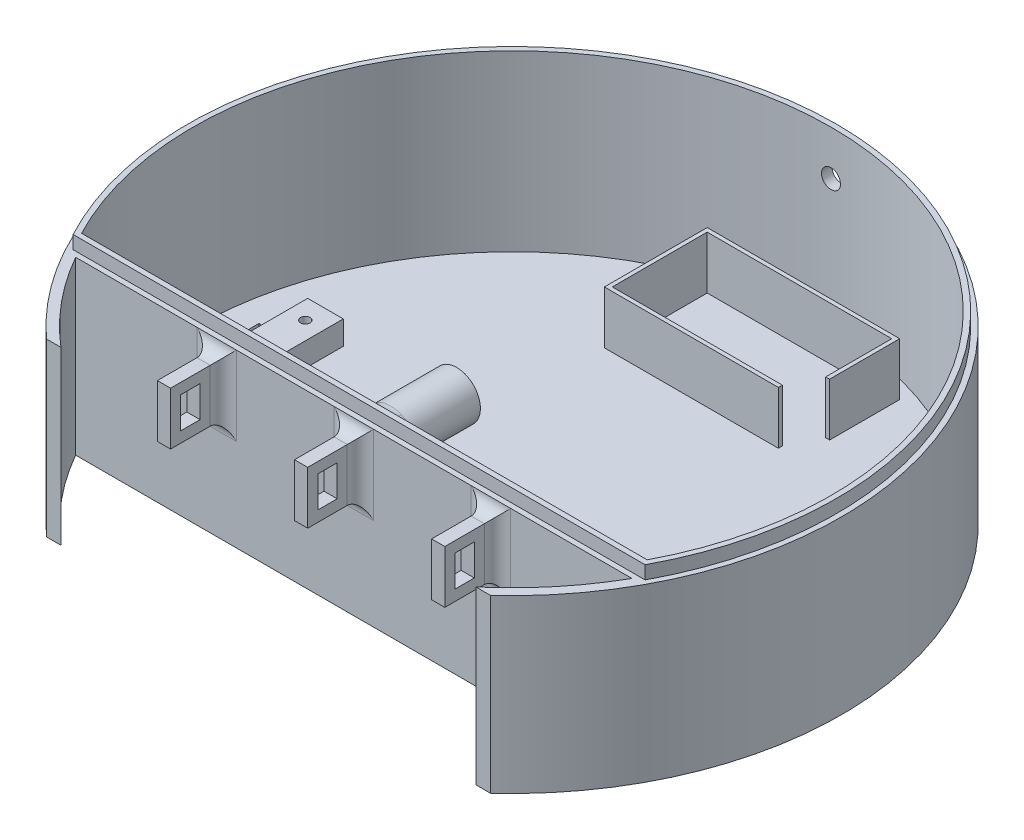
SolidWorks part; units mm, degrees
ref_plane "Plano frontal" through (0, 0, 0) normal (0, 0, 1) x (1, 0, 0)
ref_plane "Plano superior" through (0, 0, 0) normal (0, 1, 0) x (1, 0, 0)
ref_plane "Plano direito" through (0, 0, 0) normal (1, 0, 0) x (0, 0, -1)
sketch "Esboço1" plane through (0, 0, 0) normal (0, 1, 0) x (1, 0, 0)
  line L0 (-109.6586, -60) -> (109.6586, -60)
  circle A0 centre (0, 0) radius 125
  point P5 (0, -125)
  dimension "D1" = 250
  dimension "D2" = 65
extrude "Ressalto-extrusão1" add sketch "Esboço1" along normal blind 70 contours L0 A0 region at (0, 0, -22.5722)
sketch "Esboço5" plane through (0, 70, 0) normal (0, 1, 0) x (1, 0, 0)
  line L1 (-84.2002, -92.3868) -> (-78.7002, -92.3868)
  line L2 (-109.6586, -60) -> (109.6586, -60) construction
  line L3 (78.7002, -92.3868) -> (84.2002, -92.3868)
  line L4 (105.4943, -60) -> (109.6586, -60)
  line L5 (-109.6586, -60) -> (-105.4943, -60)
  arc A0 (-109.6586, -60) -> (-84.2002, -92.3868) centre (0, 0) ccw
  arc A1 (109.6586, -60) -> (84.2002, -92.3868) centre (0, 0) cw
  arc A2 (-105.4943, -60) -> (-78.7002, -92.3868) centre (0, 0) ccw
  arc A3 (78.7002, -92.3868) -> (105.4943, -60) centre (0, 0) ccw
  dimension "D1" = 5.5
  dimension "D2" = 5.5
extrude "Ressalto-extrusão4" add sketch "Esboço5" against normal up to surface (70 mm away) contours A2 L1 A0 L5 | A1 L3 A3 L4 up to face at (0, 0, -32.5)
shell "Casca1" thickness 4 removed face at (0, 70, 45.7497)
sketch "Esboço17" plane through (0, 4, 0) normal (0, 1, 0) x (1, 0, 0)
  line L0 (0, 0) -> (-50000, 0) construction
  line L1 (0, 0) -> (0, 50000) construction
  line L2 (-110, -14) -> (-100, -14)
  line L3 (-110, -14) -> (-110, 14)
  line L4 (-110, 14) -> (-100, 14)
  line L5 (-100, -14) -> (-100, 14)
  line L6 (-110, -14) -> (-100, 14) construction
  line L7 (-110, 14) -> (-100, -14) construction
  line L8 (110, 14) -> (100, -14) construction
  line L9 (110, -14) -> (100, 14) construction
  line L10 (100, -14) -> (100, 14)
  line L11 (110, 14) -> (100, 14)
  line L12 (110, -14) -> (110, 14)
  line L13 (110, -14) -> (100, -14)
  point P3 (-105, 0)
  point P15 (105, 0)
  dimension "D3" = 100
  dimension "D1" = 10
  dimension "D2" = 28
extrude "Corte-extrusão2" cut sketch "Esboço17" against normal blind 10
sketch "Esboço23" plane through (0, 70, 0) normal (0, 1, 0) x (1, 0, 0)
  line L7 (-108.4666, -58) -> (108.4666, -58)
  line L8 (-108.4666, -58) -> (108.4666, -58)
  arc A7 (108.4666, -58) -> (-108.4666, -58) centre (0, 0) ccw
  arc A8 (108.4666, -58) -> (-108.4666, -58) centre (0, 0) ccw
  dimension "D1" = 2
extrude "Corte-extrusão6" cut sketch "Esboço23" along normal blind 4 and the other way blind 5 flip side to cut
sketch "Esboço24" plane through (0, 4, 0) normal (0, 1, 0) x (1, 0, 0)
  line L0 (0, 0) -> (0, 50000) construction
  line L1 (-36.5, 91.0087) -> (49963.5, 91.0087) construction
  line L2 (-36.5, 110.5087) -> (36.5, 110.5087)
  line L3 (-36.5, 110.5087) -> (-36.5, 71.5087)
  line L4 (-36.5, 71.5087) -> (36.5, 71.5087)
  line L5 (36.5, 110.5087) -> (36.5, 71.5087)
  line L7 (35, 109.0087) -> (-35, 109.0087)
  line L8 (35, 109.0087) -> (35, 73.0087)
  line L9 (35, 73.0087) -> (-35, 73.0087)
  line L10 (-35, 109.0087) -> (-35, 73.0087)
  line L11 (35, 109.0087) -> (-35, 73.0087) construction
  line L12 (35, 73.0087) -> (-35, 109.0087) construction
  point P4 (-36.5, 91.0087)
  point P9 (0, 91.0087)
  dimension "D1" = 73
  dimension "D2" = 39
  dimension "D3" = 36.5
  dimension "D4" = 36.5
  dimension "D5" = 70
  dimension "D6" = 36
sketch "Esboço27" plane through (0, 0, 60) normal (0, 0, 1) x (1, 0, 0)
  line L0 (0, 49935) -> (0, -49935) construction
  line L1 (-105.4943, 65) -> (105.4943, 65) construction
  line L2 (104.9883, 32.5) -> (-49895.0117, 32.5) construction
  line L3 (105.4943, 0) -> (105.4943, 65) construction
  line L4 (-26, 82.5) -> (-26, -49917.5) construction
  line L5 (-49.5, 40) -> (-54.5, 40)
  line L6 (-49.5, 40) -> (-49.5, 60)
  line L7 (-49.5, 60) -> (-54.5, 60)
  line L8 (-54.5, 40) -> (-54.5, 60)
  line L9 (-49.5, 40) -> (-54.5, 60) construction
  line L10 (-49.5, 60) -> (-54.5, 40) construction
  line L11 (26, 65) -> (26, -49935) construction
  line L12 (49.5, 60) -> (54.5, 40) construction
  line L13 (49.5, 40) -> (54.5, 60) construction
  line L14 (54.5, 40) -> (54.5, 60)
  line L15 (49.5, 60) -> (54.5, 60)
  line L16 (49.5, 40) -> (49.5, 60)
  line L17 (49.5, 40) -> (54.5, 40)
  line L18 (-2.5, 60) -> (2.5, 40) construction
  line L19 (-2.5, 40) -> (2.5, 60) construction
  line L20 (2.5, 40) -> (2.5, 60)
  line L21 (-2.5, 60) -> (2.5, 60)
  line L22 (-2.5, 40) -> (-2.5, 60)
  line L23 (-2.5, 40) -> (2.5, 40)
  line L24 (-105.4943, 0) -> (105.4943, 0) construction
  point P4 (0, 65)
  point P9 (105.4943, 32.5)
  point P10 (-52, 50)
  point P23 (52, 50)
  point P28 (0, 50)
  point P29 (0, 0)
  point P30 (0, 0)
  dimension "D1" = 5
  dimension "D2" = 20
  dimension "D3" = 26
  dimension "D4" = 26
  dimension "D5" = 52
  dimension "D6" = 40
extrude "Ressalto-extrusão5" add sketch "Esboço27" along normal blind 20
fillet "Filete2" radius 5 12 edges at (52, 60, 60) (49.5, 50, 60) (52, 40, 60) (-52, 60, 60) (-54.5, 50, 60) (-52, 40, 60) (0, 40, 60) (-2.5, 50, 60) (0, 60, 60) (54.5, 50, 60) (2.5, 50, 60) (-49.5, 50, 60)
sketch "Esboço28" plane through (-49.5, 0, 0) normal (1, 0, 0) x (0, 0, -1)
  line L0 (-80, 40) -> (-65, 40) construction
  line L1 (-65, 40) -> (-65, 60) construction
  line L2 (-65, 60) -> (-80, 60) construction
  line L3 (-80, 60) -> (-80, 40) construction
  line L4 (-80, 40) -> (-65, 40) construction
  line L5 (-65, 40) -> (-65, 60) construction
  line L6 (-65, 60) -> (-80, 60) construction
  line L7 (-80, 60) -> (-80, 40) construction
  line L8 (-80, 40) -> (-65, 40)
  line L9 (-65, 40) -> (-65, 60)
  line L10 (-65, 60) -> (-80, 60)
  line L11 (-80, 60) -> (-80, 40)
  line L12 (-80, 40) -> (-65, 40)
  line L13 (-65, 40) -> (-65, 60)
  line L14 (-65, 60) -> (-80, 60)
  line L15 (-80, 60) -> (-80, 40)
  line L16 (-72.5, 42.5) -> (-72.5, -49957.5) construction
  line L17 (-75, 50) -> (49925, 50) construction
  line L18 (-80, 40) -> (-65, 40)
  line L19 (-68.816, 44.0773) -> (-76.184, 44.0773)
  line L20 (-68.816, 44.0773) -> (-68.816, 55.9227)
  line L21 (-68.816, 55.9227) -> (-76.184, 55.9227)
  line L22 (-76.184, 44.0773) -> (-76.184, 55.9227)
  line L23 (-68.816, 44.0773) -> (-76.184, 55.9227) construction
  line L24 (-68.816, 55.9227) -> (-76.184, 44.0773) construction
  line L25 (-65, 40) -> (-65, 60)
  line L26 (-65, 60) -> (-80, 60)
  line L27 (-80, 60) -> (-80, 40)
  line L28 (-80, 40) -> (-65, 40)
  line L29 (-65, 40) -> (-65, 60)
  line L30 (-65, 60) -> (-80, 60)
  line L31 (-80, 60) -> (-80, 40)
  point P6 (-72.5, 60)
  point P9 (-80, 50)
  point P10 (-72.5, 50)
  point P11 (-72.5, 50)
extrude "Corte-extrusão7" cut sketch "Esboço28" against normal blind 5 and the other way blind 104 contours L22 L19 L20 L21 region at (-49.5, 50, 72.5)
sketch "Esboço32" plane through (0, 0, 56) normal (0, 0, -1) x (-1, 0, 0)
  line L0 (0, 0) -> (0, 50000) construction
  line L2 (-105.0373, 53.0583) -> (49894.9627, 53.0583) construction
  circle A0 centre (0, 53.0583) radius 3.6
  circle A1 centre (0, 53.0583) radius 9
extrude "Corte-extrusão8" cut sketch "Esboço32" along normal blind 187 contours A0
extrude "Ressalto-extrusão6" add sketch "Esboço32<3>" along normal blind 35
sketch "Esboço32<3>" plane through (0, 0, 56) normal (0, 0, -1) x (-1, 0, 0) same geometry as "Esboço32"
extrude "Ressalto-extrusão7" add sketch "Esboço32<4>" along normal blind 6 contours A0
sketch "Esboço32<4>" plane through (0, 0, 56) normal (0, 0, -1) x (-1, 0, 0) same geometry as "Esboço32"
fillet "Filete3" radius 10 1 edges at (-9, 53.0583, 56)
extrude "Ressalto-extrusão8" add sketch "Esboço24" along normal blind 20
sketch "Esboço33" plane through (0, 4, 0) normal (0, 1, 0) x (1, 0, 0)
  line L0 (-100, -14) -> (-100, 14) construction
  line L2 (64, -48) -> (4, -48)
  line L3 (64, -48) -> (64, 32)
  line L4 (64, 32) -> (4, 32)
  line L5 (4, -48) -> (4, 32)
  line L8 (-4, -48) -> (-64, -48)
  line L9 (-4, -48) -> (-4, 42)
  line L10 (-4, 42) -> (-64, 42)
  line L11 (-64, -48) -> (-64, 42)
  line L14 (-107.2614, -56) -> (107.2614, -56) construction
  line L15 (100, 14) -> (100, -14) construction
  line L20 (5, 35.3125) -> (65, -45.3125) construction
  line L21 (5, -45.3125) -> (65, 35.3125) construction
  line L26 (-4, 45) -> (-64, -45) construction
  line L27 (-4, -45) -> (-64, 45) construction
  point P0 (35, -5)
  point P9 (-34, 0)
  point P14 (100, 0)
  point P15 (35, -5)
  point P22 (-34, 0)
  dimension "D1" = 8
  dimension "D2" = 36
  dimension "D3" = 60
  dimension "D4" = 60
  dimension "D5" = 90
  dimension "D6" = 36
  dimension "D7" = 80
  dimension "D8" = 8
sketch "Esboço34" plane through (0, 4, 0) normal (0, 1, 0) x (1, 0, 0)
  line L1 (0, 0) -> (0, 50000) construction
  line L2 (-86.5, -22.5) -> (-100, -22.5)
  line L3 (-86.5, -22.5) -> (-86.5, 22.5)
  line L4 (-86.5, 22.5) -> (-100, 22.5)
  line L5 (-100, -22.5) -> (-100, 22.5)
  line L6 (-100, -14) -> (-100, 14) construction
  line L7 (86.5, 22.5) -> (100, 22.5)
  line L8 (86.5, -22.5) -> (86.5, 22.5)
  line L9 (100, -22.5) -> (100, 22.5)
  line L10 (86.5, -22.5) -> (100, -22.5)
  circle A0 centre (-93.25, -14.875) radius 4
  circle A1 centre (-93.25, 14.875) radius 4
  circle A2 centre (-93.25, -14.875) radius 1.8
  circle A3 centre (-93.25, 14.875) radius 1.8
  circle A4 centre (93.25, -14.875) radius 1.8
  circle A5 centre (93.25, -14.875) radius 4
  circle A6 centre (93.25, 14.875) radius 4
  circle A7 centre (93.25, 14.875) radius 1.8
  point P7 (-100, 0)
  point P11 (-100, 0)
  point P19 (-93.25, -14.875)
  point P20 (-93.25, 14.875)
  line M8 (-100, 14) -> (-100, -14)
  line M14 (100, -14) -> (100, 14)
  dimension "D2" = 45
extrude "Ressalto-extrusão10" add sketch "Esboço34" along normal blind 9 contours L5 L2 L3 L4 A1 A0 M8 | A0 A2 | A1 A3 | L8 L10 L9 L7 A5 A6 M14 | A5 A4 | A6 A7 region at (-93.25, 4, 0) region at (93.25, 4, 0) region at (-97.1369, 4, 14.875) region at (-97.1369, 4, -14.875) region at (89.3631, 4, 14.875) region at (89.3631, 4, -14.875)
extrude "Corte-extrusão9" cut sketch "Esboço34<3>" against normal blind 9 contours A3 | A2 | A4 | A7
sketch "Esboço34<3>" plane through (0, 4, 0) normal (0, 1, 0) x (1, 0, 0) same geometry as "Esboço34"
extrude "Corte-extrusão10" cut sketch "Esboço34<4>" against normal blind 9 and the other way blind 5 contours A0 | A1 | A5 | A6
sketch "Esboço34<4>" plane through (0, 4, 0) normal (0, 1, 0) x (1, 0, 0) same geometry as "Esboço34"
sketch "Esboço35" plane through (36.5, 0, 0) normal (1, 0, 0) x (0, 0, -1)
  line L0 (110.5087, 24) -> (110.5087, 4) construction
  line L1 (71.5087, 24) -> (110.5087, 24)
  line L2 (71.5087, 24) -> (71.5087, 10)
  line L3 (71.5087, 10) -> (110.5087, 10)
  line L4 (110.5087, 24) -> (110.5087, 10)
  line L5 (71.5087, 4) -> (110.5087, 4) construction
  line L6 (71.5087, 24) -> (83.9364, 24)
  line L7 (71.5087, 24) -> (71.5087, 4)
  line L8 (71.5087, 4) -> (83.9364, 4)
  line L9 (83.9364, 24) -> (83.9364, 4)
  line M1 (71.5087, 4) -> (110.5087, 4)
  line M4 (71.5087, 24) -> (71.5087, 4)
extrude "Corte-extrusão13" cut sketch "Esboço35" against normal blind 7 contours L9 L1 L3 M4 | L9 L3 M4 M1 region at (36.5, 17, -77.7226) region at (36.5, 7, -77.7226)
